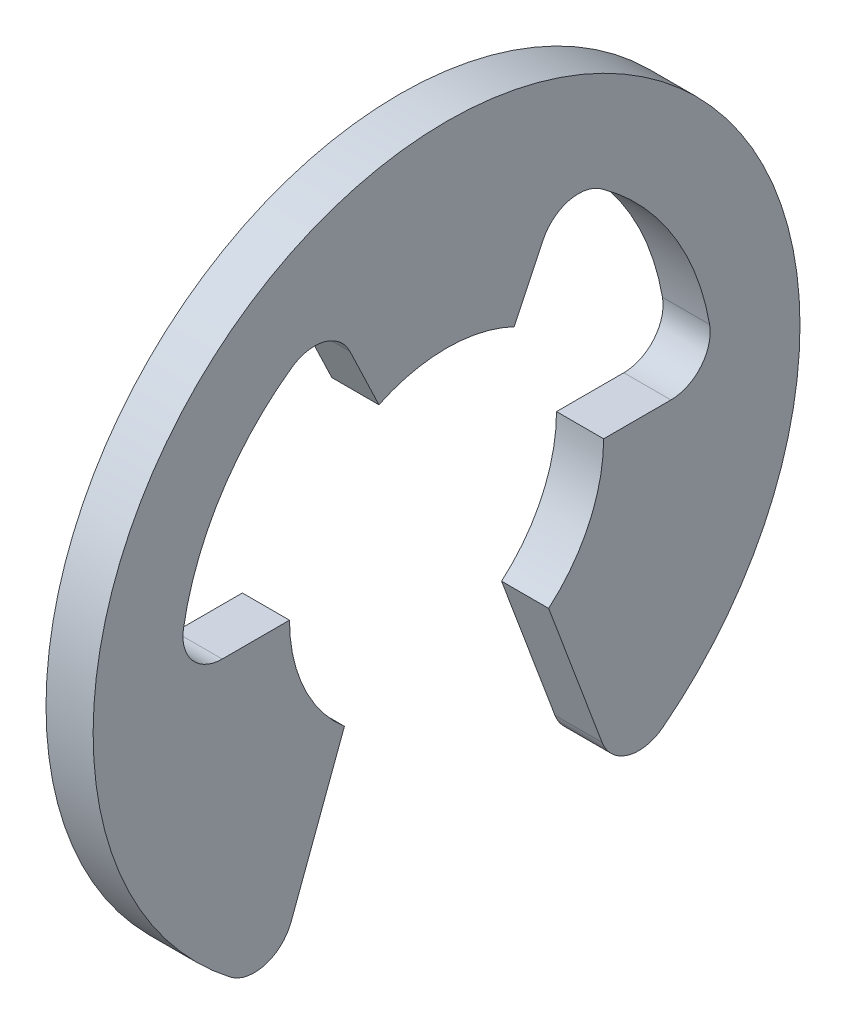
SolidWorks part; units mm, degrees
ref_plane "Front Plane" through (0, 0, 0) normal (0, 0, 1) x (1, 0, 0)
ref_plane "Top Plane" through (0, 0, 0) normal (0, 1, 0) x (1, 0, 0)
ref_plane "Right Plane" through (0, 0, 0) normal (1, 0, 0) x (0, 0, -1)
ref_axis "Axis_X" through (-0.2228, 0, 0) along (1, 0, 0)
ref_axis "Axis_Y" through (0, 4.9082, 0) along (0, -1, 0)
ref_axis "Axis_Z" through (0, 0, -4.95) along (0, 0, 1)
sketch "Sketch1" plane through (0, 0, 0) normal (1, 0, 0) x (0, 0, -1)
  line L0 (2.8566, 0) -> (2, 0)
  line L1 (1.3, -1.5199) -> (1.9799, -3.3384)
  line L2 (-1.9799, -3.3384) -> (-1.3, -1.5199)
  line L3 (-2, 0) -> (-2.8566, 0)
  line L4 (-1.2298, 2.5783) -> (-0.861, 1.8052)
  line L5 (0.861, 1.8052) -> (1.2298, 2.5783)
  line L6 (-4.5, 0) -> (4.5, 0) construction
  line L7 (0, 0) -> (0, 4.5) construction
  line L8 (0, 0) -> (-1.9373, 4.0616) construction
  line L9 (0, 0) -> (1.9373, 4.0616) construction
  line L11 (0, 0) -> (1.3, -1.5199) construction
  arc A0 (1.3, -1.5199) -> (2, 0) centre (0, 0) ccw
  arc A1 (1.9799, -3.3384) -> (2.7543, -3.5587) centre (2.4482, -3.1632) ccw
  arc A2 (2.7543, -3.5587) -> (-2.7543, -3.5587) centre (0, 0) ccw
  arc A3 (-2.7543, -3.5587) -> (-1.9799, -3.3384) centre (-2.4482, -3.1632) ccw
  arc A4 (-2, 0) -> (-1.3, -1.5199) centre (0, 0) ccw
  arc A5 (-3.3491, 0.5862) -> (-2.8566, 0) centre (-2.8566, 0.5) ccw
  arc A6 (-1.9709, 2.7705) -> (-3.3491, 0.5862) centre (0, 0) ccw
  arc A7 (-1.2298, 2.5783) -> (-1.9709, 2.7705) centre (-1.6811, 2.363) ccw
  arc A8 (0.861, 1.8052) -> (-0.861, 1.8052) centre (0, 0) ccw
  arc A9 (1.9709, 2.7705) -> (1.2298, 2.5783) centre (1.6811, 2.363) ccw
  arc A10 (3.3491, 0.5862) -> (1.9709, 2.7705) centre (0, 0) ccw
  arc A11 (2.8566, 0) -> (3.3491, 0.5862) centre (2.8566, 0.5) ccw
  circle A12 centre (0, 0) radius 2 construction
  circle A13 centre (0, 0) radius 4.5 construction
  circle A14 centre (0, 0) radius 3.4 construction
  dimension "FIX_41" = 2
  dimension "FIX_42" = 0.5
  dimension "FIX_43" = 4.5
  dimension "FIX_44" = 3.4
  dimension "FIX_45" = 1.3
  dimension "FIX_46" = 25.5
  dimension "FIX_47" = 20.5
extrude "Boss-Extrude1" add sketch "Sketch1" along normal blind 0.6
equation "\"Factor\"= 1.082532"
